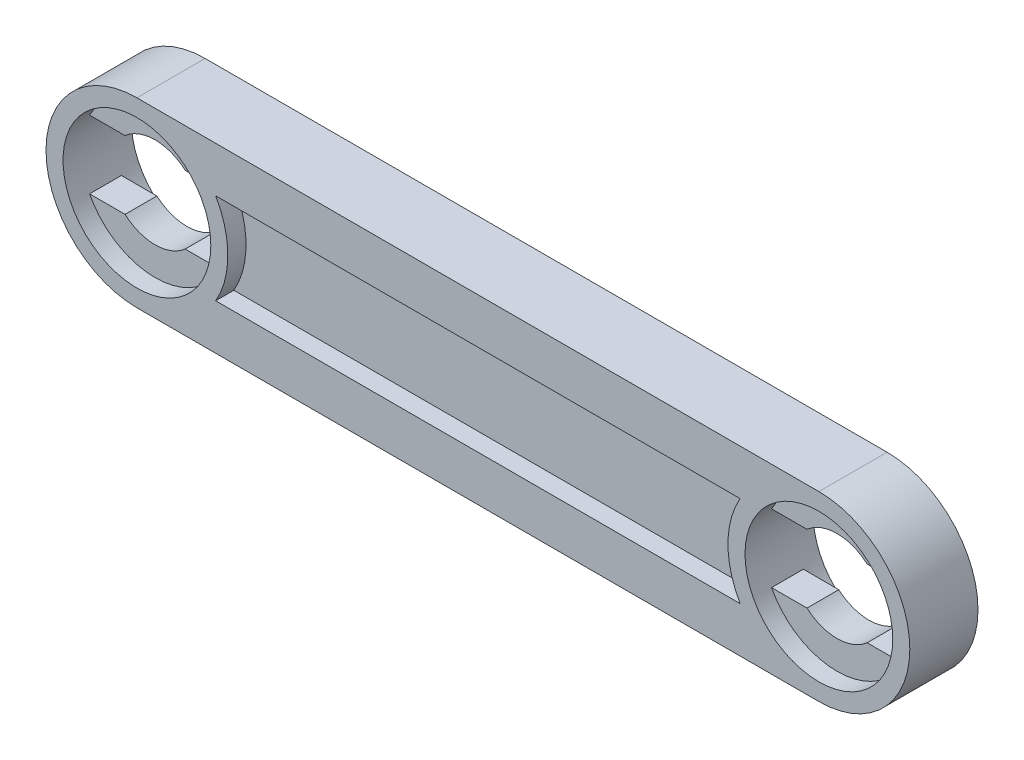
SolidWorks part; units mm, degrees
ref_plane "前视基准面" through (0, 0, 0) normal (0, 0, 1) x (1, 0, 0)
ref_plane "上视基准面" through (0, 0, 0) normal (0, 1, 0) x (1, 0, 0)
ref_plane "右视基准面" through (0, 0, 0) normal (1, 0, 0) x (0, 0, -1)
sketch "草图1" plane through (0, 0, 0) normal (0, 0, 1) x (1, 0, 0)
  line L1 (0, 4) -> (30, 4)
  line L3 (0, -4) -> (30, -4)
  arc A0 (0, 4) -> (0, -4) centre (0, 0) ccw
  arc A2 (30, -4) -> (30, 4) centre (30, 0) ccw
extrude "凸台-拉伸1" add sketch "草图1" against normal blind 3
sketch "草图2" plane through (0, 0, 0) normal (0, 0, 1) x (1, 0, 0)
  line L0 (1.3229, -1.5) -> (2.8831, -1.5)
  line L1 (-2.8831, -1.5) -> (-1.3229, -1.5)
  line L2 (1.3229, 1.5) -> (2.8831, 1.5)
  line L3 (-2.8831, 1.5) -> (-1.3229, 1.5)
  arc A0 (1.3229, 1.5) -> (-1.3229, 1.5) centre (0, 0) ccw
  arc A1 (-2.8831, 1.5) -> (-2.8831, -1.5) centre (0, 0) ccw
  arc A3 (2.8831, -1.5) -> (2.8831, 1.5) centre (0, 0) ccw
  arc A4 (-1.3229, -1.5) -> (1.3229, -1.5) centre (0, 0) ccw
extrude "切除-拉伸1" cut sketch "草图2" against normal up to next
sketch "草图3" plane through (0, 0, 0) normal (0, 0, 1) x (1, 0, 0)
  circle A1 centre (0, 0) radius 3.25
extrude "切除-拉伸2" cut sketch "草图3" against normal blind 0.8
extrude "切除-拉伸3" cut sketch "草图3<2>" along normal blind 0.8 from offset 3 offset against normal yes
sketch "草图3<2>" plane through (0, 0, 0) normal (0, 0, 1) x (1, 0, 0) same geometry as "草图3"
ref_plane "基准面1" through (15, 0, 0) normal (1, 0, 0) x (0, 0, -1)
mirror "镜向1" about plane through (15, 0, 0) normal (1, 0, 0) of "切除-拉伸3", "切除-拉伸2", "切除-拉伸1"
sketch "草图4" plane through (0, 0, 0) normal (0, 0, 1) x (1, 0, 0)
  line L0 (3.4641, 2) -> (26.5359, 2)
  line L2 (3.4641, -2) -> (26.5359, -2)
  arc A0 (3.4641, -2) -> (3.4641, 2) centre (0, 0) ccw
  arc A2 (26.5359, 2) -> (26.5359, -2) centre (30, 0) ccw
extrude "切除-拉伸4" cut sketch "草图4" against normal blind 0.8
sketch "草图5" plane through (0, 0, -3) normal (0, 0, -1) x (-1, 0, 0)
  line L1 (-26, -2) -> (-4, -2)
  line L2 (-26, -2) -> (-26, 2)
  line L3 (-26, 2) -> (-4, 2)
  line L4 (-4, -2) -> (-4, 2)
extrude "切除-拉伸5" cut sketch "草图5" against normal blind 0.8
